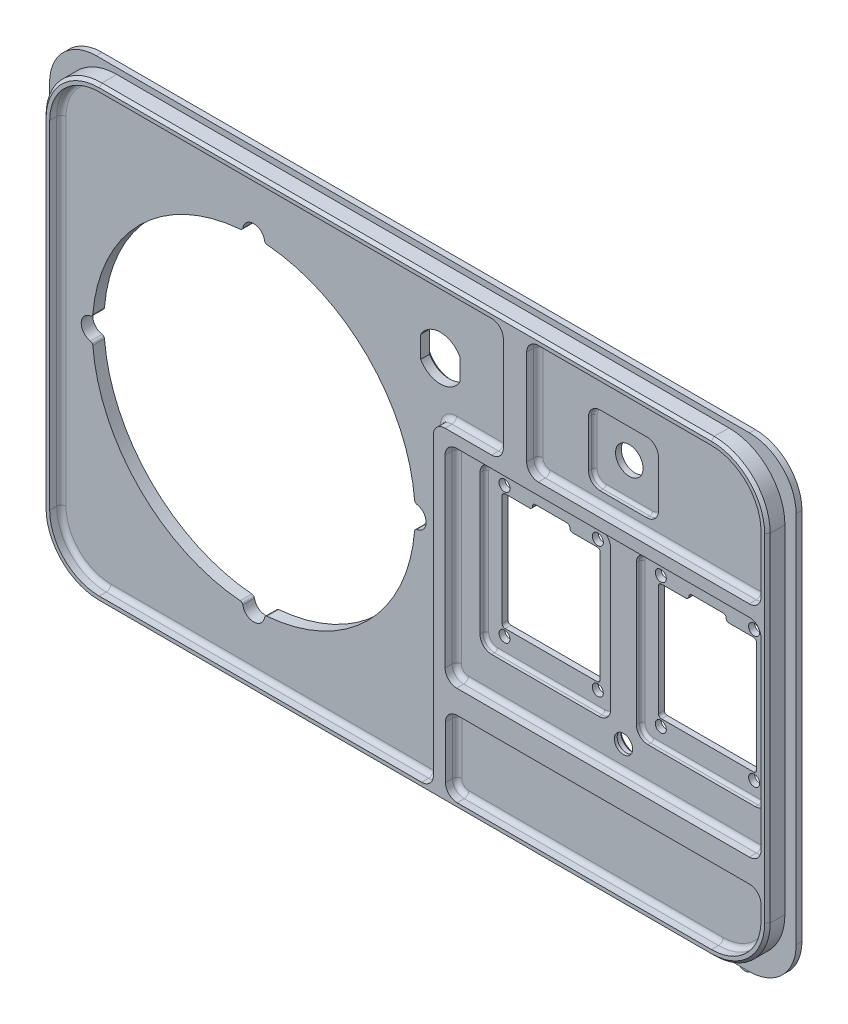
SolidWorks part; units mm, degrees
other "Markup1"
sketch "Sketch16" plane through (101.6, -64.262, 0) normal (0.6129, -0.7806, -0.1222) x (-0.7887, -0.6137, -0.0361)
ref_plane "Front Plane" through (0, 0, 0) normal (0, 0, 1) x (1, 0, 0)
ref_plane "Top Plane" through (0, 0, 0) normal (0, 1, 0) x (1, 0, 0)
ref_plane "Right Plane" through (0, 0, 0) normal (1, 0, 0) x (0, 0, -1)
sketch "Sketch2" plane through (0, 0, 0) normal (0, 0, 1) x (1, 0, 0)
  line L1 (-101.6, -63.5) -> (101.6, -63.5)
  line L2 (-101.6, -63.5) -> (-101.6, 63.5)
  line L3 (-101.6, 63.5) -> (101.6, 63.5)
  line L4 (101.6, -63.5) -> (101.6, 63.5)
  line L5 (-101.6, -63.5) -> (101.6, 63.5) construction
  line L6 (-101.6, 63.5) -> (101.6, -63.5) construction
  point P0 (0, 0)
  dimension "D1" = 203.2
  dimension "D2" = 127
extrude "Boss-Extrude1" add sketch "Sketch2" along normal blind 3.175
sketch "Sketch3" plane through (0, 0, 3.175) normal (0, 0, 1) x (1, 0, 0)
  line L0 (101.6, 63.5) -> (-101.6, 63.5) construction
  line L1 (-101.6, -63.5) -> (101.6, -63.5) construction
  line L2 (101.6, -63.5) -> (101.6, 63.5) construction
  line L3 (-101.6, 63.5) -> (-101.6, -63.5) construction
  line L21 (98.552, -45.212) -> (98.552, 46.637)
  line L22 (-83.312, -60.452) -> (83.312, -60.452)
  line L23 (-98.552, 46.637) -> (-98.552, -45.212)
  line L24 (83.312, 61.877) -> (-83.312, 61.877)
  line L25 (101.6, -63.5) -> (101.6, 63.5)
  line L26 (-101.6, -63.5) -> (101.6, -63.5)
  line L27 (-101.6, 63.5) -> (-101.6, -63.5)
  line L28 (101.6, 63.5) -> (-101.6, 63.5)
  arc A0 (83.312, 61.877) -> (98.552, 46.637) centre (83.312, 46.637) cw
  arc A1 (83.312, -60.452) -> (98.552, -45.212) centre (83.312, -45.212) ccw
  arc A2 (-83.312, -60.452) -> (-98.552, -45.212) centre (-83.312, -45.212) cw
  arc A3 (-98.552, 46.637) -> (-83.312, 61.877) centre (-83.312, 46.637) cw
  dimension "D2" = 15.24
  dimension "D1" = 1.623
  dimension "D3" = 3.048
  dimension "D4" = 3.048
  dimension "D5" = 3.048
extrude "Cut-Extrude1" cut sketch "Sketch3" against normal blind 1.5875
fillet "Fillet1" radius 12.7 4 edges at (101.6, 63.5, 0.7937) (-101.6, 63.5, 0.7937) (-101.6, -63.5, 0.7937) (101.6, -63.5, 0.7937)
sketch "Sketch13" plane through (0, 0, 3.175) normal (0, 0, 1) x (1, 0, 0)
  line L21 (98.552, -45.212) -> (98.552, 46.637) construction
  line L22 (83.312, 61.877) -> (-83.312, 61.877) construction
  line L23 (-98.552, 46.637) -> (-98.552, -45.212) construction
  line L24 (-83.312, -60.452) -> (83.312, -60.452) construction
  line L25 (96.802, -45.212) -> (96.802, 46.637)
  line L26 (-83.312, -58.702) -> (83.312, -58.702)
  line L27 (-96.802, 46.637) -> (-96.802, -45.212)
  line L28 (83.312, 60.127) -> (-83.312, 60.127)
  line L29 (96.802, -45.212) -> (96.802, 46.637)
  line L30 (-83.312, -58.702) -> (83.312, -58.702)
  line L31 (-96.802, 46.637) -> (-96.802, -45.212)
  line L32 (83.312, 60.127) -> (-83.312, 60.127)
  line L33 (98.552, -45.212) -> (98.552, 46.637)
  line L34 (83.312, 61.877) -> (-83.312, 61.877)
  line L35 (-98.552, 46.637) -> (-98.552, -45.212)
  line L36 (-83.312, -60.452) -> (83.312, -60.452)
  arc A15 (98.552, 46.637) -> (83.312, 61.877) centre (83.312, 46.637) ccw construction
  arc A16 (-83.312, 61.877) -> (-98.552, 46.637) centre (-83.312, 46.637) ccw construction
  arc A17 (-98.552, -45.212) -> (-83.312, -60.452) centre (-83.312, -45.212) ccw construction
  arc A18 (83.312, -60.452) -> (98.552, -45.212) centre (83.312, -45.212) ccw construction
  arc A19 (96.802, 46.637) -> (83.312, 60.127) centre (83.312, 46.637) ccw
  arc A20 (83.312, -58.702) -> (96.802, -45.212) centre (83.312, -45.212) ccw
  arc A21 (-96.802, -45.212) -> (-83.312, -58.702) centre (-83.312, -45.212) ccw
  arc A22 (-83.312, 60.127) -> (-96.802, 46.637) centre (-83.312, 46.637) ccw
  arc A23 (96.802, 46.637) -> (83.312, 60.127) centre (83.312, 46.637) ccw
  arc A24 (83.312, -58.702) -> (96.802, -45.212) centre (83.312, -45.212) ccw
  arc A25 (-96.802, -45.212) -> (-83.312, -58.702) centre (-83.312, -45.212) ccw
  arc A26 (-83.312, 60.127) -> (-96.802, 46.637) centre (-83.312, 46.637) ccw
  arc A27 (98.552, 46.637) -> (83.312, 61.877) centre (83.312, 46.637) ccw
  arc A28 (-83.312, 61.877) -> (-98.552, 46.637) centre (-83.312, 46.637) ccw
  arc A29 (-98.552, -45.212) -> (-83.312, -60.452) centre (-83.312, -45.212) ccw
  arc A30 (83.312, -60.452) -> (98.552, -45.212) centre (83.312, -45.212) ccw
  dimension "D1" = 1.75
extrude "Boss-Extrude2" add sketch "Sketch13" along normal blind 3.175
sketch "Sketch4" plane through (0, 0, 0) normal (0, 0, -1) x (-1, 0, 0)
  arc A0 (41.4517, 43.8396) -> (0.6104, 2.9983) centre (44.45, 0) ccw
  arc A1 (88.2896, -2.9983) -> (88.2896, 2.9983) centre (88.392, 0) ccw
  arc A2 (0.6104, 2.9983) -> (0.6104, -2.9983) centre (0.508, 0) ccw
  arc A3 (47.4483, 43.8396) -> (41.4517, 43.8396) centre (44.45, 43.942) ccw
  arc A4 (41.4517, -43.8396) -> (47.4483, -43.8396) centre (44.45, -43.942) ccw
  arc A5 (88.2896, 2.9983) -> (47.4483, 43.8396) centre (44.45, 0) ccw
  arc A6 (47.4483, -43.8396) -> (88.2896, -2.9983) centre (44.45, 0) ccw
  arc A7 (0.6104, -2.9983) -> (41.4517, -43.8396) centre (44.45, 0) ccw
  dimension "D1" = 87.884
  dimension "D3" = 3
  dimension "D2" = 44.45
extrude "big_BUTTON_HOLE" cut sketch "Sketch4" against normal through all
sketch "Sketch9" plane through (0, 0, 0) normal (0, 0, 1) x (1, 0, 0)
  circle A0 centre (-44.45, 0) radius 8
  dimension "D1" = 16
  dimension "D2" = 44.45
sketch "Sketch5" plane through (0, 0, 0) normal (0, 0, -1) x (-1, 0, 0)
  line L0 (-101.6, -50.8) -> (-101.6, 50.8) construction
  line L1 (-82.55, 15.875) -> (-82.55, 17.4625)
  line L2 (-77.47, 5.2299) -> (-77.47, -39.4161) construction
  line L3 (-34.925, 5.2299) -> (-34.925, -38.0723) construction
  line L4 (-82.55, 17.4625) -> (-72.39, 17.4625)
  line L5 (-90.805, 15.875) -> (-82.55, 15.875)
  line L6 (-90.805, 15.875) -> (-90.805, -15.875)
  line L8 (-64.135, 15.875) -> (-64.135, -15.875)
  line L9 (-90.805, 15.875) -> (-64.135, -15.875) construction
  line L10 (-90.805, -15.875) -> (-64.135, 15.875) construction
  line L11 (-48.26, 15.875) -> (-40.005, 15.875)
  line L12 (-48.26, 15.875) -> (-48.26, -15.875)
  line L14 (-21.59, 15.875) -> (-21.59, -15.875)
  line L15 (-48.26, 15.875) -> (-21.59, -15.875) construction
  line L16 (-48.26, -15.875) -> (-21.59, 15.875) construction
  line L17 (-72.39, 17.4625) -> (-72.39, 15.875)
  line L18 (-72.39, 15.875) -> (-64.135, 15.875)
  line L19 (-40.005, 15.875) -> (-40.005, 17.4625)
  line L20 (-40.005, 17.4625) -> (-29.845, 17.4625)
  line L21 (-29.845, 17.4625) -> (-29.845, 15.875)
  line L30 (-29.845, 15.875) -> (-21.59, 15.875)
  line L34 (-90.805, -15.875) -> (-64.135, -15.875)
  line L35 (-48.26, -15.875) -> (-21.59, -15.875)
  circle A0 centre (-22.225, -17.78) radius 1.5
  circle A1 centre (-47.625, -17.78) radius 1.5
  circle A2 centre (-22.225, 17.78) radius 1.5
  circle A3 centre (-47.625, 17.78) radius 1.5
  circle A4 centre (-64.77, -17.78) radius 1.5
  circle A5 centre (-64.77, 17.78) radius 1.5
  circle A6 centre (-90.17, -17.78) radius 1.5
  circle A7 centre (-90.17, 17.78) radius 1.5
  circle A8 centre (-56.1975, 40.64) radius 3.75
  circle A9 centre (-56.1975, -25.4) radius 2.5
  point P18 (-77.47, 0)
  point P23 (-34.925, 0)
  point P40 (-77.47, 17.4625)
  point P53 (-34.925, 17.4625)
  dimension "D7" = 3
  dimension "D13" = 7.5
  dimension "D15" = 5
  dimension "D1" = 25.4
  dimension "D2" = 25.4
  dimension "D3" = 35.56
  dimension "D4" = 17.145
  dimension "D5" = 11.43
  dimension "D6" = 40.64
  dimension "D8" = 12.7
  dimension "D9" = 12.7
  dimension "D10" = 31.75
  dimension "D11" = 26.67
  dimension "D12" = 1.905
  dimension "D14" = 8.5725
  dimension "D16" = 25.4
  dimension "D17" = 10.16
  dimension "D18" = 1.5875
  dimension "D19" = 26.67
extrude "OLED_CUTOUT" cut sketch "Sketch5" against normal through all
chamfer "Chamfer1" [suppressed] distance 1.5875 angle 45
sketch "Sketch8" plane through (0, 0, 0) normal (0, 0, -1) x (-1, 0, 0)
  line L0 (-1.016, 37.6888) -> (-1.016, 43.5912)
  line L1 (-11.684, 37.6888) -> (-11.684, 43.5912)
  arc A0 (-1.016, 43.5912) -> (-11.684, 43.5912) centre (-6.35, 40.64) ccw
  arc A1 (-11.684, 37.6888) -> (-1.016, 37.6888) centre (-6.35, 40.64) ccw
  dimension "D1" = 6.096
  dimension "D2" = 10.668
  dimension "D3" = 5.334
  dimension "D4" = 6.35
  dimension "D5" = 40.64
extrude "Key_switch" cut sketch "Sketch8" against normal through all
extrude "small_button" [suppressed] cut sketch "Sketch9" along normal through all
sketch "Sketch10" plane through (0, 0, 0) normal (0, 0, -1) x (-1, 0, 0)
  circle A0 centre (-56.1975, -25.4) radius 3.125
  dimension "D1" = 6.25
extrude "Cut-Extrude4" cut sketch "Sketch10" against normal blind 2.3812
sketch "Sketch11" plane through (0, 0, 3.175) normal (0, 0, 1) x (1, 0, 0)
  line L1 (46.6725, 50.165) -> (65.7225, 50.165)
  line L2 (46.6725, 50.165) -> (46.6725, 31.115)
  line L3 (46.6725, 31.115) -> (65.7225, 31.115)
  line L4 (65.7225, 50.165) -> (65.7225, 31.115)
  line L5 (46.6725, 50.165) -> (65.7225, 31.115) construction
  line L6 (46.6725, 31.115) -> (65.7225, 50.165) construction
  point P0 (56.1975, 40.64)
  dimension "D1" = 19.05
  dimension "D2" = 19.05
extrude "Cut-Extrude5" cut sketch "Sketch11" against normal blind 1.5875
sketch "Sketch12" plane through (0, 0, 3.175) normal (0, 0, 1) x (1, 0, 0)
  line L0 (34.925, 17.4625) -> (34.925, -24.701) construction
  line L1 (17.145, -22.225) -> (52.705, -22.225)
  line L2 (17.145, -22.225) -> (17.145, 22.225)
  line L3 (17.145, 22.225) -> (52.705, 22.225)
  line L4 (52.705, -22.225) -> (52.705, 22.225)
  line L5 (17.145, -22.225) -> (52.705, 22.225) construction
  line L6 (17.145, 22.225) -> (52.705, -22.225) construction
  line L7 (95.25, 22.225) -> (59.69, 22.225)
  line L8 (95.25, 22.225) -> (95.25, -22.225)
  line L9 (95.25, -22.225) -> (59.69, -22.225)
  line L10 (59.69, 22.225) -> (59.69, -22.225)
  line L11 (95.25, 22.225) -> (59.69, -22.225) construction
  line L12 (95.25, -22.225) -> (59.69, 22.225) construction
  line L13 (29.845, 17.4625) -> (40.005, 17.4625) construction
  line L14 (0, 0) -> (93.7193, 0) construction
  line L15 (77.47, 17.4625) -> (77.47, -24.701) construction
  line L16 (72.39, 17.4625) -> (82.55, 17.4625) construction
  point P0 (34.925, 0)
  point P5 (77.47, 0)
  dimension "D1" = 44.45
  dimension "D2" = 35.56
extrude "Cut-Extrude6" cut sketch "Sketch12" against normal blind 1.5875
fillet "Fillet7" radius 0.7937 16 edges at (90.805, 15.875, 0.7938) (82.55, 15.875, 0.7938) (82.55, 17.4625, 0.7938) (64.135, 15.875, 0.7938) (72.39, 17.4625, 0.7938) (72.39, 15.875, 0.7938) (48.26, 15.875, 0.7938) (40.005, 17.4625, 0.7938) (29.845, 17.4625, 0.7938) (21.59, 15.875, 0.7938) (40.005, 15.875, 0.7938) (29.845, 15.875, 0.7938) (21.59, -15.875, 0.7938) (48.26, -15.875, 0.7938) (64.135, -15.875, 0.7938) (90.805, -15.875, 0.7938)
chamfer "Chamfer2" [suppressed] distance 1.5875 angle 45
fillet "Fillet8" radius 3.175 12 edges at (95.25, 22.225, 2.3812) (59.69, 22.225, 2.3812) (59.69, -22.225, 2.3812) (95.25, -22.225, 2.3812) (52.705, -22.225, 2.3812) (17.145, -22.225, 2.3812) (52.705, 22.225, 2.3812) (17.145, 22.225, 2.3812) (65.7225, 31.115, 2.3812) (46.6725, 31.115, 2.3812) (65.7225, 50.165, 2.3812) (46.6725, 50.165, 2.3812)
fillet "Fillet9" radius 0.7937 24 edges at (47.6024, 49.2351, 1.5875) (56.1975, 50.165, 1.5875) (64.7926, 49.2351, 1.5875) (65.7225, 40.64, 1.5875) (64.7926, 32.0449, 1.5875) (56.1975, 31.115, 1.5875) (47.6024, 32.0449, 1.5875) (34.925, 22.225, 1.5875) (51.7751, 21.2951, 1.5875) (52.705, 0, 1.5875) (51.7751, -21.2951, 1.5875) (34.925, -22.225, 1.5875) (18.0749, -21.2951, 1.5875) (17.145, 0, 1.5875) (46.6725, 40.64, 1.5875) (18.0749, 21.2951, 1.5875) (94.3201, 21.2951, 1.5875) (95.25, 0, 1.5875) (94.3201, -21.2951, 1.5875) (77.47, -22.225, 1.5875) (60.6199, -21.2951, 1.5875) (59.69, 0, 1.5875) (60.6199, 21.2951, 1.5875) (77.47, 22.225, 1.5875)
chamfer "Chamfer3" distance 0.762 angle 45 8 edges at (0, -60.452, 6.35) (94.0883, -55.9883, 6.35) (-94.0883, -55.9883, 6.35) (98.552, 0.7125, 6.35) (-98.552, 0.7125, 6.35) (94.0883, 57.4133, 6.35) (-94.0883, 57.4133, 6.35) (0, 61.877, 6.35)
sketch "Sketch14" plane through (0, 0, 0) normal (0, 0, -1) x (-1, 0, 0)
  line L0 (-88.9, -63.5) -> (-88.9, -64.262)
  line L1 (-88.9, -64.262) -> (-85.725, -64.262)
  line L2 (-85.725, -64.262) -> (-85.725, -63.5)
  line L3 (88.9, -63.5) -> (-88.9, -63.5) construction
  line L4 (-85.725, -63.5) -> (-88.9, -63.5)
  point P9 (-85.725, -64.262)
  point P12 (-88.9, -64.262)
  dimension "D1" = 0.762
  dimension "D2" = 3.175
extrude "Boss-Extrude3" add sketch "Sketch14" against normal blind 1.27
mirror "Mirror1" about plane through (0, 0, 0) normal (1, 0, 0) of "Boss-Extrude3"
fillet "Fillet12" radius 1.5875 4 edges at (-85.725, -64.262, 0.635) (-88.9, -64.262, 0.635) (85.725, -64.262, 0.635) (88.9, -64.262, 0.635)
sketch "Sketch15" plane through (0, 0, 3.175) normal (0, 0, 1) x (1, 0, 0)
  line L0 (96.802, -45.212) -> (96.802, 46.637) construction
  line L1 (96.802, 27.94) -> (33.02, 27.94)
  line L2 (96.802, 27.94) -> (96.802, 24.765)
  line L3 (96.802, -38.1) -> (10.922, -38.1)
  line L4 (7.62, 27.94) -> (7.62, -58.702)
  line L5 (96.802, 24.765) -> (10.795, 24.765)
  line L6 (10.795, 24.765) -> (10.795, -31.75)
  line L7 (10.795, -31.75) -> (96.802, -31.75)
  line L8 (96.802, -31.75) -> (96.802, -38.1)
  line L9 (88.9, 63.5) -> (-88.9, 63.5) construction
  line L11 (-83.312, -58.702) -> (83.312, -58.702) construction
  line L12 (10.922, -38.1) -> (10.922, -58.702)
  line L13 (10.922, -58.702) -> (7.62, -58.702)
  line L14 (26.67, 60.127) -> (26.67, 27.94)
  line L15 (83.312, 60.127) -> (-83.312, 60.127) construction
  line L16 (33.02, 60.127) -> (33.02, 27.94)
  line L18 (26.67, 60.127) -> (33.02, 60.127)
  line L19 (26.67, 27.94) -> (7.62, 27.94)
  line L20 (101.6, -50.8) -> (101.6, 50.8) construction
  line L21 (-88.9, -63.5) -> (88.9, -63.5) construction
  dimension "D1" = 3.175
  dimension "D2" = 35.56
  dimension "D3" = 6.35
  dimension "D4" = 3.175
  dimension "D5" = 3.302
  dimension "D6" = 6.35
  dimension "D7" = 68.58
  dimension "D8" = 25.4
  dimension "D9" = 93.98
extrude "Boss-Extrude5" add sketch "Sketch15" along direction (0, 0, 1) on the side of the normal blind 3.175
fillet "Fillet13" radius 3.175 14 edges at (26.67, 60.127, 4.7625) (26.67, 27.94, 4.7625) (7.62, 27.94, 4.7625) (96.802, -38.1, 4.7625) (10.922, -38.1, 4.7625) (10.922, -58.702, 4.7625) (33.02, 60.127, 4.7625) (33.02, 27.94, 4.7625) (96.802, 27.94, 4.7625) (96.802, -31.75, 4.7625) (96.802, 24.765, 4.7625) (10.795, -31.75, 4.7625) (10.795, 24.765, 4.7625) (7.62, -58.702, 4.7625)
fillet "Fillet14" radius 1.27 36 edges at (-39.4335, -58.702, 3.175) (-92.8509, -54.7509, 3.175) (-96.802, 0.7125, 3.175) (-92.8509, 56.1759, 3.175) (-29.9085, 60.127, 3.175) (25.7401, 59.1971, 3.175) (26.67, 44.0335, 3.175) (25.7401, 28.8699, 3.175) (17.145, 27.94, 3.175) (8.5499, 27.0101, 3.175) (11.8519, -39.0299, 3.175) (10.922, -48.401, 3.175) (11.8519, -57.7721, 3.175) (48.7045, -58.702, 3.175) (92.8509, -54.7509, 3.175) (96.802, -43.2435, 3.175) (95.8721, -39.0299, 3.175) (11.7249, 23.8351, 3.175) (10.795, -3.4925, 3.175) (11.7249, -30.8201, 3.175) (53.7985, -31.75, 3.175) (95.8721, -30.8201, 3.175) (96.802, -3.4925, 3.175) (95.8721, 23.8351, 3.175) (92.8509, 56.1759, 3.175) (96.802, 38.876, 3.175) (95.8721, 28.8699, 3.175) (64.911, 27.94, 3.175) (33.9499, 28.8699, 3.175) (33.02, 44.0335, 3.175) (33.9499, 59.1971, 3.175) (7.62, -15.381, 3.175) (53.862, -38.1, 3.175) (53.7985, 24.765, 3.175) (59.7535, 60.127, 3.175) (6.6901, -57.7721, 3.175)
chamfer "Chamfer4" distance 0.762 angle 45 1 edges at (53.0725, -25.4, 0)
chamfer "Chamfer5" distance 0.762 angle 45 4 edges at (6.35, 46.736, 0) (11.684, 40.64, 0) (1.016, 40.64, 0) (6.35, 34.544, 0)
fillet "Fillet15" radius 0.7937 8 edges at (-88.2896, 2.9983, 1.5875) (-88.2896, -2.9983, 1.5875) (-47.4483, -43.8396, 1.5875) (-41.4517, -43.8396, 1.5875) (-0.6104, -2.9983, 1.5875) (-0.6104, 2.9983, 1.5875) (-41.4517, 43.8396, 1.5875) (-47.4483, 43.8396, 1.5875)
equation "\".0750.100000in\"=0.1"
